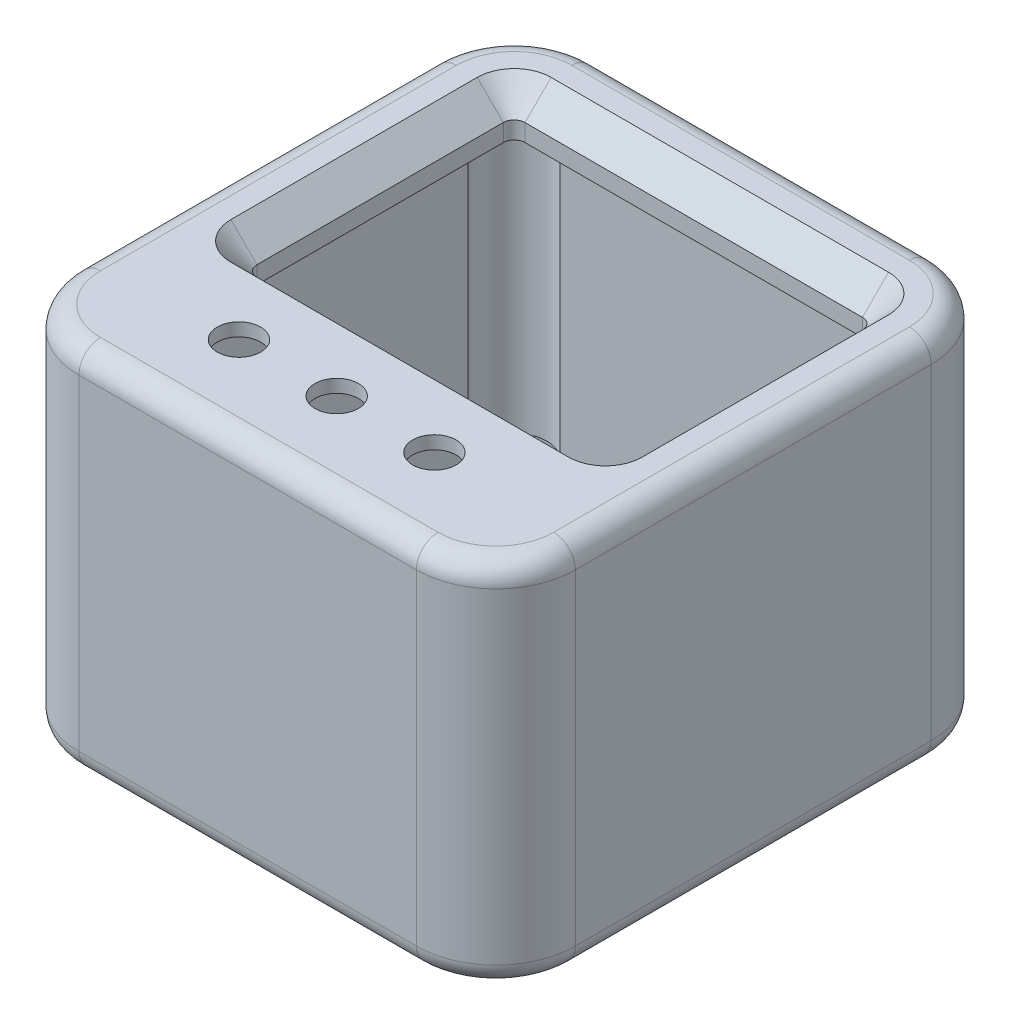
SolidWorks part; units mm, degrees
ref_plane "前视基准面" through (0, 0, 0) normal (0, 0, 1) x (1, 0, 0)
ref_plane "上视基准面" through (0, 0, 0) normal (0, 1, 0) x (1, 0, 0)
ref_plane "右视基准面" through (0, 0, 0) normal (1, 0, 0) x (0, 0, -1)
sketch "草图1" plane through (0, 0, 0) normal (0, 1, 0) x (1, 0, 0)
  line L1 (-11.43, -11.85) -> (11.43, -11.85)
  line L2 (-11.43, -11.85) -> (-11.43, 11.85)
  line L3 (-11.43, 11.85) -> (11.43, 11.85)
  line L4 (11.43, -11.85) -> (11.43, 11.85)
  line L5 (-11.43, -11.85) -> (11.43, 11.85) construction
  line L6 (-11.43, 11.85) -> (11.43, -11.85) construction
  point P0 (0, 0)
  dimension "D1" = 22.86
  dimension "D2" = 23.7
extrude "凸台-拉伸1" add sketch "草图1" along normal blind 17
sketch "草图2" plane through (0, 0, 0) normal (0, -1, 0) x (1, 0, 0)
  line L8 (9.43, -9.85) -> (9.43, 9.85)
  line L9 (9.43, 9.85) -> (-9.43, 9.85)
  line L10 (-9.43, 9.85) -> (-9.43, -9.85)
  line L11 (-9.43, -9.85) -> (9.43, -9.85)
  line L12 (9.43, -9.85) -> (9.43, 9.85)
  line L13 (9.43, 9.85) -> (-9.43, 9.85)
  line L14 (-9.43, 9.85) -> (-9.43, -9.85)
  line L15 (-9.43, -9.85) -> (9.43, -9.85)
  dimension "D1" = 2
extrude "切除-拉伸1" cut sketch "草图2" against normal offset from surface (15 mm away) 2 up to face at (0, 17, 0)
fillet "圆角1" radius 3.66 4 edges at (11.43, 8.5, -11.85) (-11.43, 8.5, -11.85) (11.43, 8.5, 11.85) (-11.43, 8.5, 11.85)
sketch "草图3" plane through (0, 17, 0) normal (0, 1, 0) x (1, 0, 0)
  circle A7 centre (0, -7.75) radius 1
  circle A9 centre (-4.5, -7.75) radius 1
  circle A10 centre (4.5, -7.75) radius 1
  dimension "D2" = 3
extrude "切除-拉伸2" cut sketch "草图3" against normal through all contours A7 | A10 | A9 region at (0, 17, 7.75) region at (4.5, 17, 7.75)
sketch "草图4" plane through (0, 17, 0) normal (0, 1, 0) x (1, 0, 0)
  line L0 (-8.27, 8.69) -> (-8.27, -3.65)
  line L5 (-8.73, 9.15) -> (8.73, 9.15)
  line L6 (-8.73, 9.15) -> (-8.73, -4.11)
  line L7 (-8.73, -4.11) -> (8.73, -4.11)
  line L8 (8.73, 9.15) -> (8.73, -4.11)
  line L9 (-8.27, -3.65) -> (8.27, -3.65)
  line L10 (8.27, 8.69) -> (8.27, -3.65)
  line L11 (-8.27, 8.69) -> (8.27, 8.69)
  line L12 (-8.73, -4.11) -> (8.73, -4.11) construction
  dimension "D1" = 0.46
extrude "切除-拉伸3" cut sketch "草图4" against normal through all contours L11 L0 L9 L10 region at (0, 17, -2.52)
fillet "圆角2" radius 0.5 4 edges at (8.27, 16, 3.65) (-8.27, 16, 3.65) (-8.27, 16, -8.69) (8.27, 16, -8.69)
chamfer "倒角1" distance 1.2 angle 45 8 edges at (-8.27, 17, -2.52) (-8.1236, 17, -8.5436) (-8.1236, 17, 3.5036) (0, 17, -8.69) (0, 17, 3.65) (8.1236, 17, -8.5436) (8.1236, 17, 3.5036) (8.27, 17, -2.52)
fillet "圆角3" radius 1 16 edges at (10.358, 17, -10.778) (11.43, 17, 0) (10.358, 17, 10.778) (0, 17, 11.85) (-10.358, 17, 10.778) (-11.43, 17, 0) (-10.358, 17, -10.778) (0, 17, -11.85) (0, 0, -11.85) (-10.358, 0, -10.778) (-11.43, 0, 0) (-10.358, 0, 10.778) (0, 0, 11.85) (10.358, 0, 10.778) (11.43, 0, 0) (10.358, 0, -10.778)
sketch "草图5" plane through (0, 0, 0) normal (0, -1, 0) x (1, 0, 0)
  line L0 (-7.77, 8.19) -> (-9.43, 9.85) construction
  line L2 (7.77, 8.19) -> (9.43, 9.85) construction
  line L3 (7.77, -8.19) -> (9.43, -9.85) construction
  line L4 (-9.43, -9.85) -> (9.43, -9.85) construction
  line L5 (9.43, -9.85) -> (-9.43, -9.85) construction
  line L6 (-7.77, -8.19) -> (-9.43, -9.85) construction
  line L7 (-7.77, 10.5376) -> (7.77, 10.5376)
  line L8 (10.1176, 8.19) -> (10.1176, -8.19)
  line L9 (-7.77, -10.5376) -> (7.77, -10.5376)
  line L10 (-10.1176, 8.19) -> (-10.1176, -8.19)
  arc A0 (-7.77, 10.5376) -> (-10.1176, 8.19) centre (-7.77, 8.19) ccw
  arc A1 (-10.1176, -8.19) -> (-7.77, -10.5376) centre (-7.77, -8.19) ccw
  arc A2 (7.77, -10.5376) -> (10.1176, -8.19) centre (7.77, -8.19) ccw
  arc A3 (10.1176, 8.19) -> (7.77, 10.5376) centre (7.77, 8.19) ccw
extrude "切除-拉伸4" cut sketch "草图5" against normal blind 2
sketch "草图6" plane through (0, 2, 0) normal (0, -1, 0) x (1, 0, 0)
  line L0 (7.77, 8.19) -> (9.43, 9.85) construction
  line L1 (7.77, -8.19) -> (9.43, -9.85) construction
  line L2 (9.43, 9.85) -> (9.43, -9.85) construction
  line L3 (-7.77, -8.19) -> (-9.43, -9.85) construction
  line L4 (-7.77, 8.19) -> (-9.43, 9.85) construction
  circle A0 centre (-7.77, 8.19) radius 2.3476 construction
  circle A1 centre (7.77, 8.19) radius 2.3476 construction
  circle A2 centre (7.77, -8.19) radius 2.3476 construction
  circle A3 centre (-7.77, -8.19) radius 2.3476 construction
  circle A4 centre (8.3693, 8.7893) radius 1.5
  circle A5 centre (8.3693, -8.7893) radius 1.5
  circle A6 centre (-8.3693, -8.7893) radius 1.5
  circle A7 centre (-8.3693, 8.7893) radius 1.5
  dimension "D1" = 3
extrude "切除-拉伸5_可根据铣刀经济半径修改R角" cut sketch "草图6" against normal up to surface (13 mm away) up to face at (-4.5, 15, 6.75)
sketch "草图7" [suppressed] plane through (0, 0, 0) normal (0, -1, 0) x (1, 0, 0)
  line L0 (7.77, 10.5376) -> (-7.77, 10.5376) construction
  line L1 (-10.1176, 8.19) -> (-10.1176, -8.19) construction
  line L2 (-7.77, -10.5376) -> (7.77, -10.5376) construction
  line L3 (10.1176, -8.19) -> (10.1176, 8.19) construction
  line L4 (7.77, 10.5376) -> (-7.77, 10.5376) construction
  line L5 (-10.1176, 8.19) -> (-10.1176, -8.19) construction
  line L6 (-7.77, -10.5376) -> (7.77, -10.5376) construction
  line L7 (10.1176, -8.19) -> (10.1176, 8.19) construction
  line L8 (7.77, 10.3876) -> (-7.77, 10.3876)
  line L9 (-9.9676, 8.19) -> (-9.9676, -8.19)
  line L10 (-7.77, -10.3876) -> (7.77, -10.3876)
  line L11 (9.9676, -8.19) -> (9.9676, 8.19)
  line L12 (9.9676, 0) -> (-9.9676, 0) construction
  arc A0 (10.1176, 8.19) -> (7.77, 10.5376) centre (7.77, 8.19) ccw construction
  arc A1 (-7.77, 10.5376) -> (-10.1176, 8.19) centre (-7.77, 8.19) ccw construction
  arc A2 (-10.1176, -8.19) -> (-7.77, -10.5376) centre (-7.77, -8.19) ccw construction
  arc A3 (7.77, -10.5376) -> (10.1176, -8.19) centre (7.77, -8.19) ccw construction
  arc A4 (10.1176, 8.19) -> (7.77, 10.5376) centre (7.77, 8.19) ccw construction
  arc A5 (-7.77, 10.5376) -> (-10.1176, 8.19) centre (-7.77, 8.19) ccw construction
  arc A6 (-10.1176, -8.19) -> (-7.77, -10.5376) centre (-7.77, -8.19) ccw construction
  arc A7 (7.77, -10.5376) -> (10.1176, -8.19) centre (7.77, -8.19) ccw construction
  arc A8 (9.9676, 8.19) -> (7.77, 10.3876) centre (7.77, 8.19) ccw
  arc A9 (-7.77, 10.3876) -> (-9.9676, 8.19) centre (-7.77, 8.19) ccw
  arc A10 (-9.9676, -8.19) -> (-7.77, -10.3876) centre (-7.77, -8.19) ccw
  arc A11 (7.77, -10.3876) -> (9.9676, -8.19) centre (7.77, -8.19) ccw
  dimension "D1" = 0.15
sketch "草图8" plane through (0, 15, 0) normal (0, -1, 0) x (1, 0, 0)
  line L0 (-9.43, -7.7287) -> (-9.43, 7.7287) construction
  line L1 (-9.43, 5.35) -> (9.43, 5.35)
  line L2 (-9.43, 5.35) -> (-9.43, 9.85)
  line L3 (-9.43, 9.85) -> (9.43, 9.85)
  line L4 (9.43, 5.35) -> (9.43, 9.85)
  line L5 (9.43, 7.7287) -> (9.43, -7.7287) construction
  line L6 (-9.23, 5.65) -> (7.2, 5.65) construction
  line L7 (-7.3087, 9.85) -> (7.3087, 9.85) construction
  dimension "D1" = 0.3
extrude "切除-拉伸5" cut sketch "草图8" against normal blind 0.4
ref_plane "基准面1" through (2.8, 16.14, 9.05) normal (0, 0, -1) x (-1, 0, 0)
sketch "草图11" plane through (0, 15.4, 0) normal (0, -1, 0) x (1, 0, 0)
  line L0 (-6.2, 6.45) -> (-6.2, 9.05) construction
  line L1 (-3.2, 6.05) -> (-5.8, 6.05) construction
  line L2 (-2.8, 6.45) -> (-2.8, 9.05) construction
  line L3 (-3.2, 9.45) -> (-5.8, 9.45) construction
  line L4 (-6.2, 6.45) -> (-6.2, 9.05)
  line L5 (-3.2, 6.05) -> (-5.8, 6.05)
  line L6 (-2.8, 6.45) -> (-2.8, 9.05)
  line L7 (-3.2, 9.45) -> (-5.8, 9.45)
  line L8 (-1.7, 6.45) -> (-1.7, 9.05) construction
  line L9 (1.3, 6.05) -> (-1.3, 6.05) construction
  line L10 (1.7, 6.45) -> (1.7, 9.05) construction
  line L11 (1.3, 9.45) -> (-1.3, 9.45) construction
  line L12 (-1.7, 6.45) -> (-1.7, 9.05)
  line L13 (1.3, 6.05) -> (-1.3, 6.05)
  line L14 (1.7, 6.45) -> (1.7, 9.05)
  line L15 (1.3, 9.45) -> (-1.3, 9.45)
  line L16 (2.8, 6.45) -> (2.8, 9.05) construction
  line L17 (5.8, 6.05) -> (3.2, 6.05) construction
  line L18 (6.2, 6.45) -> (6.2, 9.05) construction
  line L19 (5.8, 9.45) -> (3.2, 9.45) construction
  line L20 (2.8, 6.45) -> (2.8, 9.05)
  line L21 (5.8, 6.05) -> (3.2, 6.05)
  line L22 (6.2, 6.45) -> (6.2, 9.05)
  line L23 (5.8, 9.45) -> (3.2, 9.45)
  line L24 (2.7, 6.45) -> (2.7, 9.05)
  line L25 (5.8, 9.55) -> (3.2, 9.55)
  line L26 (6.3, 6.45) -> (6.3, 9.05)
  line L27 (5.8, 5.95) -> (3.2, 5.95)
  line L28 (-1.8, 6.45) -> (-1.8, 9.05)
  line L29 (1.3, 9.55) -> (-1.3, 9.55)
  line L30 (1.8, 6.45) -> (1.8, 9.05)
  line L31 (1.3, 5.95) -> (-1.3, 5.95)
  line L32 (-6.3, 6.45) -> (-6.3, 9.05)
  line L33 (-3.2, 5.95) -> (-5.8, 5.95)
  line L34 (-2.7, 6.45) -> (-2.7, 9.05)
  line L35 (-3.2, 9.55) -> (-5.8, 9.55)
  arc A0 (-5.8, 9.45) -> (-6.2, 9.05) centre (-5.8, 9.05) ccw construction
  arc A1 (-6.2, 6.45) -> (-5.8, 6.05) centre (-5.8, 6.45) ccw construction
  arc A2 (-3.2, 6.05) -> (-2.8, 6.45) centre (-3.2, 6.45) ccw construction
  arc A3 (-2.8, 9.05) -> (-3.2, 9.45) centre (-3.2, 9.05) ccw construction
  arc A4 (-5.8, 9.45) -> (-6.2, 9.05) centre (-5.8, 9.05) ccw
  arc A5 (-6.2, 6.45) -> (-5.8, 6.05) centre (-5.8, 6.45) ccw
  arc A6 (-3.2, 6.05) -> (-2.8, 6.45) centre (-3.2, 6.45) ccw
  arc A7 (-2.8, 9.05) -> (-3.2, 9.45) centre (-3.2, 9.05) ccw
  arc A8 (-1.7, 6.45) -> (-1.3, 6.05) centre (-1.3, 6.45) ccw construction
  arc A9 (1.3, 6.05) -> (1.7, 6.45) centre (1.3, 6.45) ccw construction
  arc A10 (1.7, 9.05) -> (1.3, 9.45) centre (1.3, 9.05) ccw construction
  arc A11 (-1.3, 9.45) -> (-1.7, 9.05) centre (-1.3, 9.05) ccw construction
  arc A12 (-1.7, 6.45) -> (-1.3, 6.05) centre (-1.3, 6.45) ccw
  arc A13 (1.3, 6.05) -> (1.7, 6.45) centre (1.3, 6.45) ccw
  arc A14 (1.7, 9.05) -> (1.3, 9.45) centre (1.3, 9.05) ccw
  arc A15 (-1.3, 9.45) -> (-1.7, 9.05) centre (-1.3, 9.05) ccw
  arc A16 (2.8, 6.45) -> (3.2, 6.05) centre (3.2, 6.45) ccw construction
  arc A17 (5.8, 6.05) -> (6.2, 6.45) centre (5.8, 6.45) ccw construction
  arc A18 (6.2, 9.05) -> (5.8, 9.45) centre (5.8, 9.05) ccw construction
  arc A19 (3.2, 9.45) -> (2.8, 9.05) centre (3.2, 9.05) ccw construction
  arc A20 (2.8, 6.45) -> (3.2, 6.05) centre (3.2, 6.45) ccw
  arc A21 (5.8, 6.05) -> (6.2, 6.45) centre (5.8, 6.45) ccw
  arc A22 (6.2, 9.05) -> (5.8, 9.45) centre (5.8, 9.05) ccw
  arc A23 (3.2, 9.45) -> (2.8, 9.05) centre (3.2, 9.05) ccw
  arc A24 (3.2, 9.55) -> (2.7, 9.05) centre (3.2, 9.05) ccw
  arc A25 (6.3, 9.05) -> (5.8, 9.55) centre (5.8, 9.05) ccw
  arc A26 (5.8, 5.95) -> (6.3, 6.45) centre (5.8, 6.45) ccw
  arc A27 (2.7, 6.45) -> (3.2, 5.95) centre (3.2, 6.45) ccw
  arc A28 (-1.3, 9.55) -> (-1.8, 9.05) centre (-1.3, 9.05) ccw
  arc A29 (1.8, 9.05) -> (1.3, 9.55) centre (1.3, 9.05) ccw
  arc A30 (1.3, 5.95) -> (1.8, 6.45) centre (1.3, 6.45) ccw
  arc A31 (-1.8, 6.45) -> (-1.3, 5.95) centre (-1.3, 6.45) ccw
  arc A32 (-5.8, 9.55) -> (-6.3, 9.05) centre (-5.8, 9.05) ccw
  arc A33 (-6.3, 6.45) -> (-5.8, 5.95) centre (-5.8, 6.45) ccw
  arc A34 (-3.2, 5.95) -> (-2.7, 6.45) centre (-3.2, 6.45) ccw
  arc A35 (-2.7, 9.05) -> (-3.2, 9.55) centre (-3.2, 9.05) ccw
  circle M2 centre (4.5, 7.75) radius 1
  circle M7 centre (-4.5, 7.75) radius 1
  circle M8 centre (0, 7.75) radius 1
  dimension "D1" = 0.1
  dimension "D2" = 0.1
  dimension "D3" = 0.1
extrude "切除-拉伸6" cut sketch "草图11" against normal blind 1 contours L23 A23 L20 A20 L21 A21 L22 A22 M2 | L24 A27 L27 A26 L26 A25 L25 A24 A23 L23 A22 L22 A21 L21 A20 L20 | L28 A31 L31 A30 L30 A29 L29 A28 A15 L15 A14 L14 A13 L13 A12 L12 | L15 A15 L12 A12 L13 A13 L14 A14 M8 | L34 A35 L35 A32 L32 A33 L33 A34 A7 L6 A6 L5 A5 L4 A4 L7 | L6 A7 L7 A4 L4 A5 L5 A6 M7 region at (-6.1519, 15.4, 7.75) region at (-1.6519, 15.4, 7.75) region at (2.8481, 15.4, 7.75) region at (2.7509, 15.4, 7.75) region at (-1.7491, 15.4, 7.75) region at (-6.2491, 15.4, 7.75)
sketch "草图12" plane through (0, 15, 0) normal (0, -1, 0) x (1, 0, 0)
  line L0 (-9.43, 5.35) -> (9.43, 5.35) construction
  line L1 (-9.43, -7.7287) -> (-9.43, 7.7287) construction
  line L2 (9.43, 7.7287) -> (9.43, -7.7287) construction
  circle A0 centre (8.3693, 8.7893) radius 1.5
  circle A1 centre (-8.3693, 8.7893) radius 1.5
  circle A2 centre (8.93, 5.35) radius 0.5
  circle A3 centre (-8.93, 5.35) radius 0.5
  dimension "D1" = 1
extrude "切除-拉伸7" cut sketch "草图12" against normal up to surface (0.4 mm away) up to face at (0, 15.4, 7.75)
chamfer "倒角2" distance 0.3 distance2 1 24 edges at (6.1536, 15.4, 9.4036) (4.5, 15.4, 9.55) (6.3, 15.4, 7.75) (2.8464, 15.4, 9.4036) (6.1536, 15.4, 6.0964) (2.7, 15.4, 7.75) (4.5, 15.4, 5.95) (2.8464, 15.4, 6.0964) (1.6536, 15.4, 9.4036) (0, 15.4, 9.55) (1.8, 15.4, 7.75) (-1.6536, 15.4, 9.4036) (1.6536, 15.4, 6.0964) (-1.8, 15.4, 7.75) (0, 15.4, 5.95) (-1.6536, 15.4, 6.0964) (-2.7, 15.4, 7.75) (-2.8464, 15.4, 6.0964) (-2.8464, 15.4, 9.4036) (-4.5, 15.4, 5.95) (-4.5, 15.4, 9.55) (-6.1536, 15.4, 6.0964) (-6.1536, 15.4, 9.4036) (-6.3, 15.4, 7.75) first distance on face at (0, 15.4, 7.75)
sketch "草图13" plane through (0, 0, 0) normal (0, -1, 0) x (1, 0, 0)
  line L0 (-10.43, 8.19) -> (-10.43, -8.19) construction
  line L1 (-7.77, -10.85) -> (7.77, -10.85) construction
  line L2 (10.43, -8.19) -> (10.43, 8.19) construction
  line L3 (7.77, 10.85) -> (-7.77, 10.85) construction
  line L4 (-10.43, 8.19) -> (-10.43, -8.19)
  line L5 (-7.77, -10.85) -> (7.77, -10.85)
  line L6 (10.43, -8.19) -> (10.43, 8.19)
  line L7 (7.77, 10.85) -> (-7.77, 10.85)
  arc A0 (-7.77, 10.85) -> (-10.43, 8.19) centre (-7.77, 8.19) ccw construction
  arc A1 (-10.43, -8.19) -> (-7.77, -10.85) centre (-7.77, -8.19) ccw construction
  arc A2 (7.77, -10.85) -> (10.43, -8.19) centre (7.77, -8.19) ccw construction
  arc A3 (10.43, 8.19) -> (7.77, 10.85) centre (7.77, 8.19) ccw construction
  arc A4 (-7.77, 10.85) -> (-10.43, 8.19) centre (-7.77, 8.19) ccw
  arc A5 (-10.43, -8.19) -> (-7.77, -10.85) centre (-7.77, -8.19) ccw
  arc A6 (7.77, -10.85) -> (10.43, -8.19) centre (7.77, -8.19) ccw
  arc A7 (10.43, 8.19) -> (7.77, 10.85) centre (7.77, 8.19) ccw
extrude "切除-拉伸8" [suppressed] cut sketch "草图13" against normal up to surface (2 mm away) up to face at (0, 2, 10.2807)
